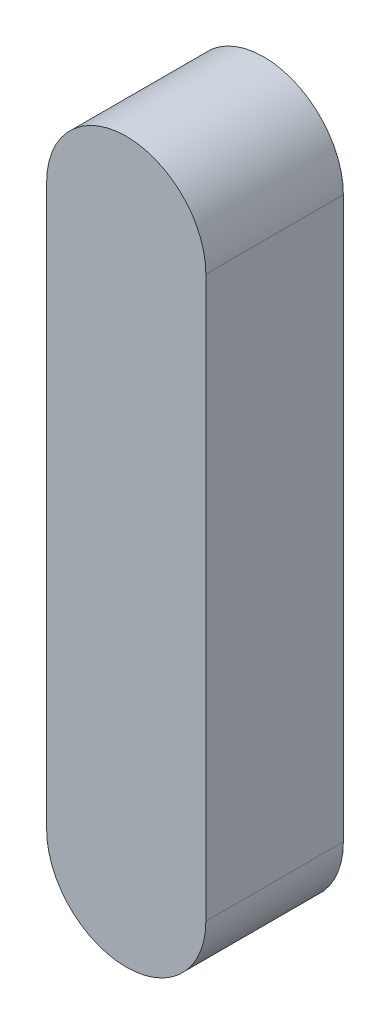
SolidWorks part; units mm, degrees
note: '?' marks a value the reader was unsure of.
ref_plane "Front Plane" through (0, 0, 0) normal (0, 0, 1) x (1, 0, 0)
ref_plane "Top Plane" through (0, 0, 0) normal (0, 1, 0) x (1, 0, 0)
ref_plane "Right Plane" through (0, 0, 0) normal (1, 0, 0) x (0, 0, -1)
sketch "Stem Block Sketch" plane through (0, 0, 0) normal (0, 0, 1) x (1, 0, 0)
  line L0 (0, 0) -> (0, 448.2566) construction
  line L1 (-63.6765, 0) -> (-63.6765, 448.2566)
  line L2 (63.6765, 0) -> (63.6765, 448.2566)
  line L3 (0, -63.6765) -> (3.5376, -67.21) construction
  line L4 (-325.0397, -396.1681) -> (-562.1186, -633.5217) construction
  arc A0 (-63.6765, 0) -> (63.6765, 0) centre (0, 0) ccw
  arc A1 (63.6765, 448.2566) -> (-63.6765, 448.2566) centre (0, 448.2566) ccw
  point P3 (0, 224.1283)
  dimension "D1" = 127.353
  dimension "D2" = 5
extrude "Stem Block Extrude" add sketch "Stem Block Sketch" against normal offset from surface 5 and the other way offset from surface (55 mm away) 5
ref_axis "Axis of Rotation" through (0, 0, 5.5) along (0, 0, -1)?
